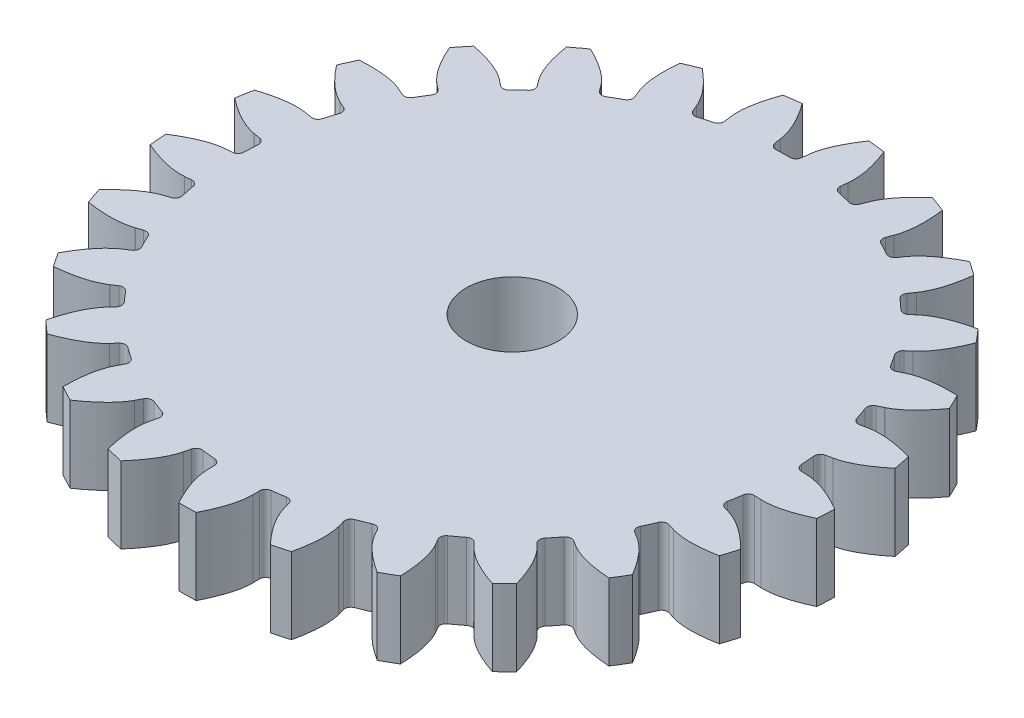
SolidWorks part; units mm, degrees
ref_plane "Front Plane" through (0, 0, 0) normal (0, 0, 1) x (1, 0, 0)
ref_plane "Top Plane" through (0, 0, 0) normal (0, 1, 0) x (1, 0, 0)
ref_plane "Right Plane" through (0, 0, 0) normal (1, 0, 0) x (0, 0, -1)
sketch "Sketch1" plane through (0, 0, 0) normal (0, 1, 0) x (1, 0, 0)
  line L0 (0, 37.59) -> (0, 0) construction
  line L1 (0, 0) -> (37.59, 0) construction
  line L2 (0, 0) -> (37.1272, 5.8804) construction
  line L3 (0, 0) -> (35.7502, 11.6159) construction
  line L4 (0, 0) -> (33.4929, 17.0655) construction
  line L5 (0, 0) -> (30.4109, 22.0948) construction
  line L6 (0, 0) -> (26.5801, 26.5801) construction
  line L7 (0, 0) -> (22.0948, 30.4109) construction
  line L8 (0, 0) -> (17.0655, 33.4929) construction
  line L9 (0, 0) -> (11.6159, 35.7502) construction
  line L10 (0, 0) -> (5.8804, 37.1272) construction
  line L11 (0, 0) -> (0, 37.59) construction
  line L12 (26.5801, 26.5801) -> (30.7521, 22.4082)
  line L13 (22.0948, 30.4109) -> (31.6412, 23.4751)
  line L14 (17.0655, 33.4929) -> (32.8363, 25.4573)
  line L15 (11.6159, 35.7502) -> (34.0609, 28.4574)
  line L16 (32.1078, 19.5473) -> (0, 0) construction
  line L17 (5.8804, 37.1272) -> (35.0172, 32.5124)
  line L18 (30.4421, 25.9476) -> (0, 0) construction
  line L19 (26.633, 26.5272) -> (30.4109, 22.0948)
  line L20 (26.633, 26.5272) -> (25.4191, 25.4925)
  line L21 (30.4109, 22.0948) -> (29.1971, 21.0602)
  circle A0 centre (0, 0) radius 37.59
  circle A1 centre (0, 0) radius 43.2
  circle A2 centre (0, 0) radius 36
  circle A3 centre (0, 0) radius 40 construction
  spline S0 degree 3 poles (30.4109, 22.0948) (30.5298, 22.194) (31.5423, 23.1408) (33.6026, 26.4986) (34.6352, 30.0559) (35.0172, 32.5124) knots 0 0 0 0 0.040059 0.359467 1 1 1 1
  spline S1 degree 3 poles (26.633, 26.5272) (26.7497, 26.6288) (27.845, 27.4785) (31.4867, 28.9809) (35.1627, 29.437) (37.6487, 29.4251) knots 0 0 0 0 0.040059 0.359467 1 1 1 1
  point P4 (32.1078, 19.5473)
  point P6 (32.0093, 23.9876)
  point P18 (0, 0)
  point P25 (30.4421, 25.9476)
  dimension "D10" = 29.5
  dimension "D11" = 72
  dimension "D9" = 75.18
  dimension "D3" = 86.4
  dimension "D19" = 80
  dimension "D2" = 9
  dimension "D4" = 5.9
  dimension "D5" = 9
  dimension "D6" = 11.8
  dimension "D7" = 17.7
  dimension "D8" = 23.6
  dimension "D12" = 9
  dimension "D13" = 9
  dimension "D14" = 9
  dimension "D15" = 9
  dimension "D16" = 9
  dimension "D17" = 9
  dimension "D18" = 9
  dimension "D20" = 2.51
extrude "Boss-Extrude2" add sketch "Sketch1" along normal blind 10 contours S1 L14 S0 A1 | S1 L12 S0 L14 | S1 A0 S0 L12 | L19 A0 | A2 L21 L19 L20 | A2 region at (29.8765, 0, -25.3036) region at (28.5564, 0, -24.3403) region at (27.9447, 0, -23.8189) region at (29.6087, 0, -23.3551) region at (0, 0, 0) region at (31.4968, 0, -27.3254)
sketch "Sketch2" plane through (0, 0, 0) normal (0, 0, 1) x (1, 0, 0)
  line L0 (0, 0) -> (0, 23.545) construction
  line L1 (-36, 0) -> (36, 0) construction
pattern_circular "CirPattern1" count 25 over 360 about axis through (0, 0, 0) along (0, 1, 0) of "Boss-Extrude2" reverse direction yes
sketch "Sketch3" plane through (0, 10, 0) normal (0, 1, 0) x (1, 0, 0)
  circle A0 centre (0, 0) radius 6.0429
extrude "Cut-Extrude1" cut sketch "Sketch3" against normal blind 10
fillet "Fillet1" radius 0.8 100 edges at (23.9608, 5, -28.9636) (18.2808, 5, -31.0131) (19.1993, 5, -32.3171) (16.005, 5, -34.0124) (9.9939, 5, -34.585) (10.5591, 5, -36.0765) (7.0437, 5, -36.9242) (6.8671, 5, -35.339) (1.0789, 5, -35.9838) (1.2555, 5, -37.569) (-2.3603, 5, -37.5158) (-2.1371, 5, -35.9365) (-7.9038, 5, -35.1217) (-8.1269, 5, -36.701) (-11.6159, 5, -35.7502) (-11.007, 5, -34.276) (-16.3899, 5, -32.0527) (-16.9988, 5, -33.5269) (-20.1417, 5, -31.7383) (-19.1853, 5, -30.4618) (-23.8461, 5, -26.9697) (-24.8025, 5, -28.2461) (-27.4019, 5, -25.7321) (-26.1581, 5, -24.7336) (-29.804, 5, -20.1921) (-31.0478, 5, -21.1906) (-32.9404, 5, -18.1091) (-31.4873, 5, -17.4513) (-33.8892, 5, -12.1457) (-35.3423, 5, -12.8036) (-36.409, 5, -9.3483) (-34.8381, 5, -9.0725) (-35.8451, 5, -3.3363) (-37.4161, 5, -3.612) (-37.59, 5, 0) (-35.9998, 5, -0.1236) (-35.5486, 5, 5.6829) (-37.1388, 5, 5.8064) (-36.409, 5, 9.3483) (-34.8995, 5, 8.8331) (-33.0185, 5, 14.3449) (-34.5281, 5, 14.8601) (-32.9404, 5, 18.1091) (-31.6064, 5, 17.2348) (-28.4138, 5, 22.1056) (-29.7477, 5, 22.98) (-27.4019, 5, 25.7321) (-26.3273, 5, 24.5535) (-22.0236, 5, 28.4773) (-23.0983, 5, 29.656) (-20.1417, 5, 31.7383) (-19.394, 5, 30.3294) (-14.2497, 5, 33.0597) (-14.9975, 5, 34.4686) (-11.6159, 5, 35.7502) (-11.2421, 5, 34.1997) (-5.5804, 5, 35.5649) (-5.9543, 5, 37.1154) (-2.3603, 5, 37.5158) (-2.3838, 5, 35.921) (3.4395, 5, 35.8353) (3.463, 5, 37.4301) (7.0437, 5, 36.9242) (6.6243, 5, 35.3853) (12.2434, 5, 33.8541) (12.6627, 5, 35.393) (16.005, 5, 34.0124) (15.2162, 5, 32.6262) (20.2779, 5, 29.7457) (21.0668, 5, 31.132) (23.9608, 5, 28.9636) (22.8519, 5, 27.8171) (27.0383, 5, 23.7683) (28.1471, 5, 24.9148) (30.4109, 5, 22.0948) (29.0518, 5, 21.2601) (32.0998, 5, 16.2974) (33.4589, 5, 17.1322) (34.9503, 5, 13.8378) (33.4263, 5, 13.3673) (35.1443, 5, 7.8025) (36.6683, 5, 8.273) (37.2936, 5, 4.7113) (35.7004, 5, 4.6346) (35.9806, 5, -1.1826) (37.5737, 5, -1.1059) (37.2936, 5, -4.7113) (35.7314, 5, -4.3894) (34.5561, 5, -10.0935) (36.1183, 5, -10.4154) (34.9503, 5, -13.8378) (33.5172, 5, -13.1375) (30.9603, 5, -18.3701) (32.3933, 5, -19.0704) (30.4109, 5, -22.0948) (29.1971, 5, -21.0602) (25.4191, 5, -25.4925) (26.633, 5, -26.5272) (15.4398, 5, -32.521) (23.0423, 5, -27.6596)
equation "\"num_teeth\"= 25"
equation "\"pressure_angle\"= 20"
equation "\"pitch_dia\"= 80"
equation "\"module\"= \"pitch_dia\" / \"num_teeth\""
equation "\"addendum\"= \"module\""
equation "\"dedendum\"= 1.25 * \"module\""
equation "\"base_dia\"= 2 * ( ( \"pitch_dia\" / 2 ) * cos ( \"pressure_angle\" ) )"
equation "\"circular_pitch\"= pi * \"module\""
equation "\"tooth_thickness\"= \"circular_pitch\" / 2"
equation "\"add_circle\"= \"pitch_dia\" + ( 2 * \"addendum\" )"
equation "\"ded_circle\"= \"pitch_dia\" - ( 2 * \"dedendum\" )"
